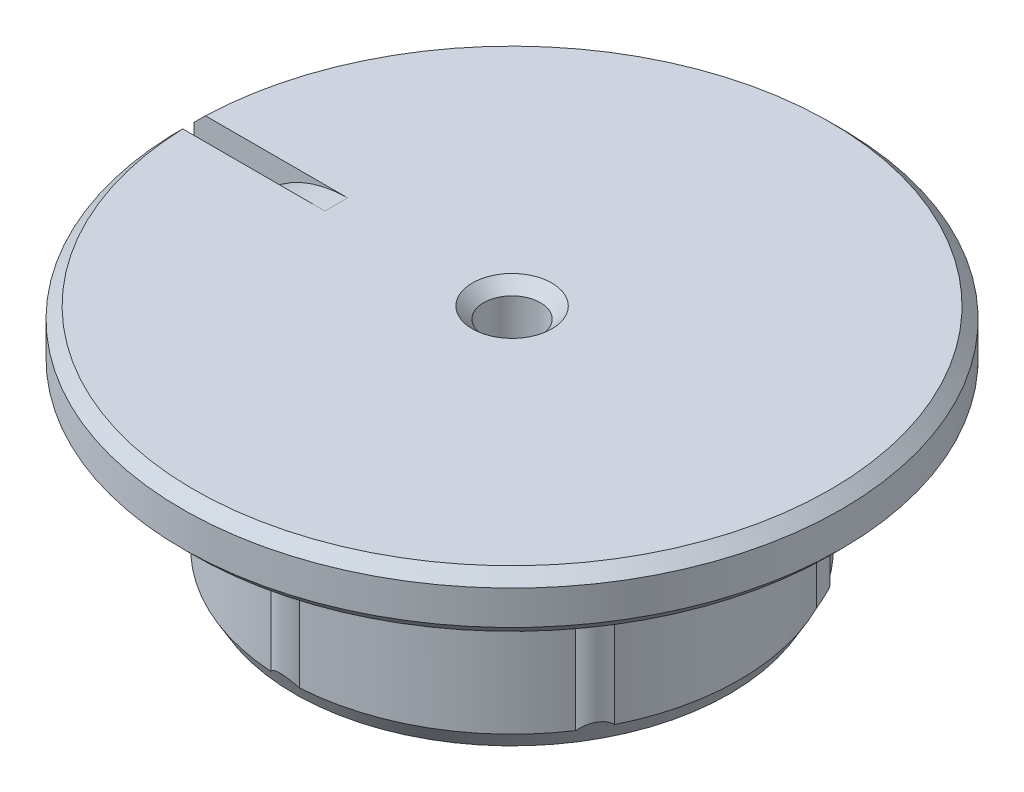
SolidWorks part; units mm, degrees
ref_plane "Front Plane" through (0, 0, 0) normal (0, 0, 1) x (1, 0, 0)
ref_plane "Top Plane" through (0, 0, 0) normal (0, 1, 0) x (1, 0, 0)
ref_plane "Right Plane" through (0, 0, 0) normal (1, 0, 0) x (0, 0, -1)
sketch "Sketch1" plane through (0, 0, 0) normal (0, 0, 1) x (1, 0, 0)
  line L0 (0, 0) -> (0, 30415.8317) construction
  line L1 (0, 0) -> (20, 0)
  line L2 (20, 0) -> (20, 15)
  line L3 (20, 15) -> (29, 15)
  line L4 (29, 15) -> (29, 20)
  line L5 (29, 20) -> (2.5, 20)
  line L6 (2.5, 20) -> (2.5, 10)
  line L7 (2.5, 10) -> (0, 10)
  line L9 (0, 10) -> (0, 0)
  dimension "D1" = 40
  dimension "D2" = 5
  dimension "D3" = 15
  dimension "D4" = 5
  dimension "D5" = 10
  dimension "D6" = 9
revolve "Revolve1" add sketch "Sketch1" angle 360 about L0
sketch "Sketch2" plane through (0, 0, 0) normal (0, -1, 0) x (1, 0, 0)
  arc A0 (-1.25, 19.9609) -> (1.25, 19.9609) centre (0, 18.4888) cw
  circle A1 centre (0, 0) radius 20 construction
  circle A2 centre (0, 0) radius 20 construction
  arc A3 (-1.25, 19.9609) -> (-16.6616, 11.063) centre (0, 0) ccw
  arc A4 (16.6616, 11.063) -> (17.9116, 8.8979) centre (16.0117, 9.2444) cw
  arc A5 (17.9116, -8.8979) -> (16.6616, -11.063) centre (16.0117, -9.2444) cw
  arc A6 (1.25, -19.9609) -> (-1.25, -19.9609) centre (0, -18.4888) cw
  arc A7 (-16.6616, -11.063) -> (-17.9116, -8.8979) centre (-16.0117, -9.2444) cw
  arc A8 (-17.9116, 8.8979) -> (-16.6616, 11.063) centre (-16.0117, 9.2444) cw
  arc A9 (-17.9116, 8.8979) -> (-17.9116, -8.8979) centre (0, 0) ccw
  arc A10 (-16.6616, -11.063) -> (-1.25, -19.9609) centre (0, 0) ccw
  arc A11 (1.25, -19.9609) -> (16.6616, -11.063) centre (0, 0) ccw
  arc A12 (17.9116, -8.8979) -> (17.9116, 8.8979) centre (0, 0) ccw
  arc A13 (16.6616, 11.063) -> (1.25, 19.9609) centre (0, 0) ccw
  point P27 (0, 0)
  dimension "D2" = 20.42
  dimension "D1" = 2.5
  dimension "D3" = 6
extrude "Boss-Extrude1" add sketch "Sketch2" against normal offset from surface (10 mm away) 5 up to face at (0, 15, -29)
sketch "Sketch3" plane through (0, 0, 0) normal (0, 0, 1) x (1, 0, 0)
  line L0 (-21, 3.2321) -> (-18.5566, -1)
  line L1 (-18.5566, -1) -> (-21, -1)
  line L2 (-21, -1) -> (-21, 3.2321)
  line L3 (-20, 0) -> (-17.9116, 0) construction
  dimension "D1" = 0.75
  dimension "D2" = 1
  dimension "D3" = 1
  dimension "D4" = 60
ref_axis "Axis1" through (0, 29.3369, 0) along (0, -1, 0)
revolve "Cut-Revolve1" cut sketch "Sketch3" angle 360 about axis through (0, 29.3369, 0) along (0, -1, 0)
chamfer "Chamfer1" distance 1 angle 45 3 edges at (0, 20, -2.5) (0, 15, -29) (0, 20, -29)
sketch "Sketch4" plane through (0, 0, 0) normal (0, -1, 0) x (1, 0, 0)
  line L0 (-24.13, 1) -> (-100, 1)
  line L1 (-100, -1) -> (-24.13, -1)
  line L2 (-100, 1) -> (-100, -1)
  line L3 (-24.13, -1) -> (-24.13, 1)
  point P5 (-100, 0)
  dimension "D1" = 2
  dimension "D2" = 100
  dimension "D3" = 24.13
extrude "Cut-Extrude1" cut sketch "Sketch4" against normal through all
fillet "Fillet1" radius 10 1 edges at (-24.13, 20, 0)
equation "\"D3@Sketch4\"=1.9in/2"
